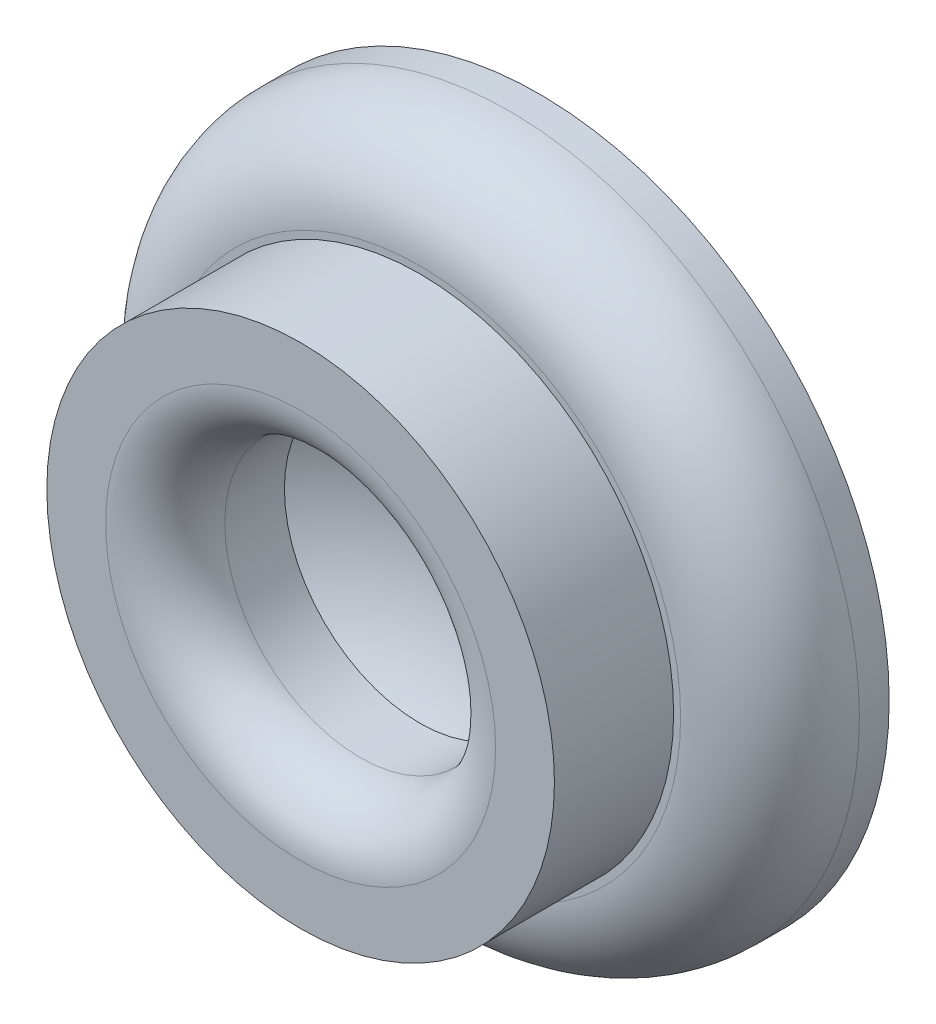
SolidWorks part; units mm, degrees
ref_plane "Front" through (0, 0, 0) normal (0, 0, 1) x (1, 0, 0)
ref_plane "Top" through (0, 0, 0) normal (0, 1, 0) x (1, 0, 0)
ref_plane "Right" through (0, 0, 0) normal (1, 0, 0) x (0, 0, -1)
sketch "Sketch1" plane through (0, 0, 0) normal (0, 0, 1) x (1, 0, 0)
  circle A0 centre (0, 0) radius 17.629
extrude "Boss-Extrude1" add sketch "Sketch1" along normal blind 6
sketch "Sketch2" plane through (0, 0, 6) normal (0, 0, 1) x (1, 0, 0)
  circle A0 centre (0, 0) radius 12.7774
  circle A1 centre (0, 0) radius 6.8182
extrude "Boss-Extrude2" add sketch "Sketch2" along normal blind 6
fillet "Fillet1" radius 4.5 1 edges at (17.629, 0, 6)
fillet "Fillet2" radius 3 1 edges at (6.8182, 0, 12)
dome "Dome1" faces to dome 1 distance 2 reverse direction yes elliptical dome no face at (6.8182, 0, 6) parameters "D1"=2
